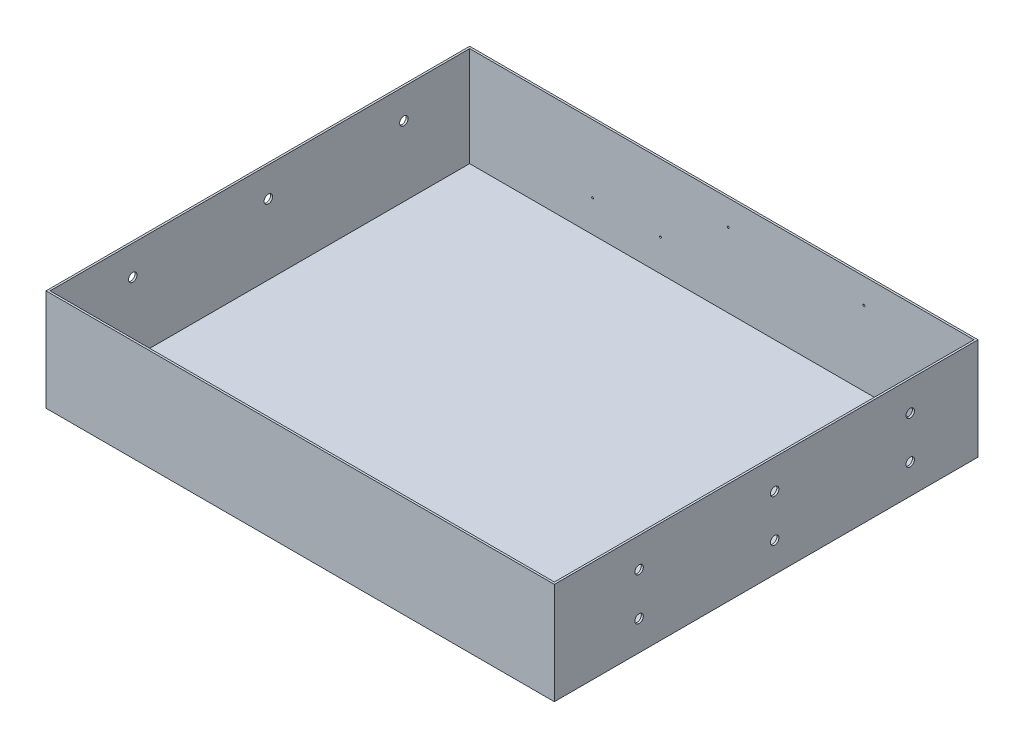
SolidWorks part; units mm, degrees
material "6061 Alloy"
ref_plane "Front Plane" through (0, 0, 0) normal (0, 0, 1) x (1, 0, 0)
ref_plane "Top Plane" through (0, 0, 0) normal (0, 1, 0) x (1, 0, 0)
ref_plane "Right Plane" through (0, 0, 0) normal (1, 0, 0) x (0, 0, -1)
other "Configuration Table"
sketch "Sketch1" plane through (0, 0, 0) normal (0, 1, 0) x (1, 0, 0)
  line L1 (-508, 508) -> (254, 508)
  line L2 (-508, 508) -> (-508, -127)
  line L3 (-508, -127) -> (254, -127)
  line L4 (254, 508) -> (254, -127)
  dimension "D1" = 508
  dimension "D2" = 635
  dimension "D3" = 762
  dimension "D4" = 508
extrude "Extrude1" add sketch "Sketch1" along normal blind 152.4
shell "Shell1" thickness 3.048 removed face at (-127, 152.4, -190.5)
sketch "Sketch2" plane through (-508, 0, 0) normal (-1, 0, 0) x (0, 0, 1)
  line L0 (-508, 152.4) -> (-508, 0) construction
  line L1 (-504.952, 152.4) -> (123.952, 152.4) construction
  circle A0 centre (-406.4, 107.95) radius 6.35
  dimension "D1" = 12.7
  dimension "D2" = 101.6
  dimension "D3" = 44.45
extrude "Connector mount--Cut-Extrude1" cut sketch "Sketch2" against normal through all
pattern_linear "LPattern1" count 3 spacing 203.2 along (0, 0, 1) of face at (-504.952, 107.95, -412.75)
pattern_linear "LPattern5" count 3 spacing 203.2 along (0, 0, 1) count 2 spacing 63.5 along (0, -1, 0) of face at (250.952, 107.95, -400.05)
sketch "Sketch3" plane through (0, 0, -508) normal (0, 0, -1) x (-1, 0, 0)
  line L0 (-250.952, 152.4) -> (-250.952, 3.048) construction
  line L1 (-250.952, 152.4) -> (504.952, 152.4) construction
  circle A0 centre (-85.852, 114.3) radius 1.524
  dimension "D1" = 3.048
  dimension "D3" = 38.1
  dimension "D2" = 165.1
extrude "Clip Mount --Cut-Extrude2" cut sketch "Sketch3" against normal blind 39.624
pattern_linear "LPattern2" count 5 spacing 101.6 along (-1, 0, 0) count 2 spacing 63.5 along (0, -1, 0) skipping (0, 1), (1, 0), (1, 1), (2, 1), (3, 0), (4, 0) of face at (87.376, 114.3, -504.952)
sketch "Sketch4" plane through (0, 0, 127) normal (0, 0, 1) x (1, 0, 0)
  circle A0 centre (-411.3748, 76.774) radius 6.35
  dimension "D1" = 12.7
extrude "Lower Connector Mnt--Cut-Extrude1" [suppressed] cut sketch "Sketch4" against normal up to surface (3.048 mm away)
pattern_linear "LPattern3" [suppressed] count 3 spacing 228.6 of bodies 106
sketch "Sketch5" plane through (0, 3.048, 0) normal (0, 1, 0) x (-1, 0, 0)
  line L0 (-250.952, 123.952) -> (-250.952, -504.952) construction
  line L1 (-250.952, -504.952) -> (504.952, -504.952) construction
  circle A0 centre (-111.252, -327.152) radius 1.524
  dimension "D1" = 3.048
  dimension "D2" = 139.7
  dimension "D3" = 177.8
extrude "Cut-Extrude1" [suppressed] cut sketch "Sketch5" against normal up to surface (3.048 mm away)
pattern_linear "LPattern4" [suppressed] count 3 spacing 127 count 5 spacing 127 of bodies 108
